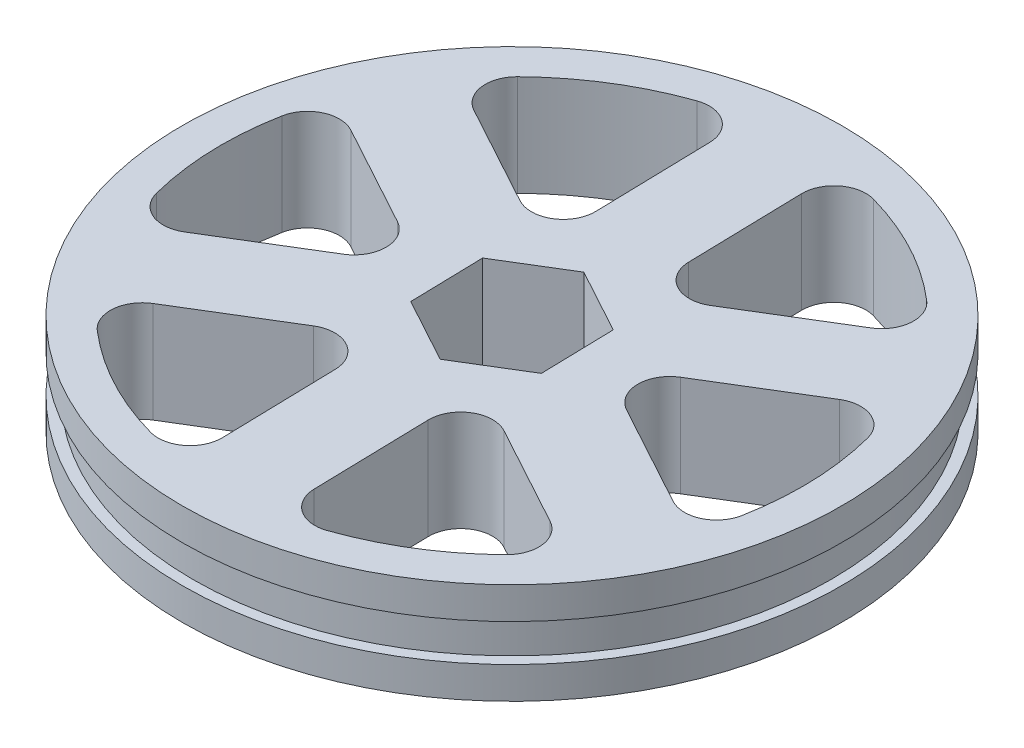
SolidWorks part; units mm, degrees
ref_plane "Front Plane" through (0, 0, 0) normal (0, 0, 1) x (1, 0, 0)
ref_plane "Top Plane" through (0, 0, 0) normal (0, 1, 0) x (1, 0, 0)
ref_plane "Right Plane" through (0, 0, 0) normal (1, 0, 0) x (0, 0, -1)
sketch "Sketch1" plane through (0, 0, 0) normal (0, 1, 0) x (1, 0, 0)
  circle A0 centre (0, 0) radius 31
  circle A1 centre (0, 0) radius 30
extrude "Boss-Extrude1" add sketch "Sketch1" along normal blind 9.5 contours A1
extrude "Boss-Extrude3" add sketch "Sketch1<4>" along normal blind 3
sketch "Sketch1<4>" plane through (0, 0, 0) normal (0, 1, 0) x (1, 0, 0) same geometry as "Sketch1"
sketch "Sketch4" plane through (0, 9.5, 0) normal (0, 1, 0) x (1, 0, 0)
  circle A0 centre (0, 0) radius 31
extrude "Boss-Extrude4" add sketch "Sketch4" against normal blind 3
sketch "Sketch6" plane through (0, 9.5, 0) normal (0, 1, 0) x (1, 0, 0)
  line L1 (-6.0822, 3.3176) -> (-5.9142, -3.6086)
  line L2 (-5.9142, -3.6086) -> (0.168, -6.9262)
  line L3 (0.168, -6.9262) -> (6.0822, -3.3176)
  line L4 (6.0822, -3.3176) -> (5.9142, 3.6086)
  line L5 (5.9142, 3.6086) -> (-0.168, 6.9262)
  line L6 (-0.168, 6.9262) -> (-6.0822, 3.3176)
  circle A0 centre (0, 0) radius 6 construction
extrude "Cut-Extrude1" cut sketch "Sketch6" against normal through all
sketch "Sketch7" plane through (0, 9.5, 0) normal (0, 1, 0) x (1, 0, 0)
  line L2 (-4.4273, 7.256) -> (-21.8367, 16.7521)
  line L3 (-4.4273, 7.256) -> (-4.9123, 27.2501)
  arc A0 (-21.8367, 16.7521) -> (-4.9123, 27.2501) centre (0.4198, -0.2375) cw
  dimension "D1" = 60
extrude "Cut-Extrude2" cut sketch "Sketch7" against normal through all contours L3 A0 L2
fillet "Fillet1" radius 3 3 edges at (-4.4273, 4.75, -7.256) (-4.9123, 4.75, -27.2501) (-21.8367, 4.75, -16.7521)
pattern_circular "CirPattern1" count 6 every 60 about axis through (0, 9.5, 0) along (0, 1, 0) of "Cut-Extrude2", "Fillet1"
